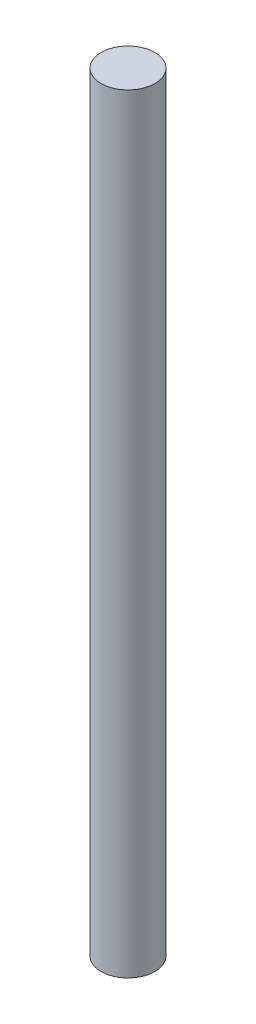
SolidWorks part; units mm, degrees
ref_plane "前视基准面" through (0, 0, 0) normal (0, 0, 1) x (1, 0, 0)
ref_plane "上视基准面" through (0, 0, 0) normal (0, 1, 0) x (1, 0, 0)
ref_plane "右视基准面" through (0, 0, 0) normal (1, 0, 0) x (0, 0, -1)
other "Configuration Table"
sketch "草图1" plane through (0, 0, 0) normal (0, 1, 0) x (1, 0, 0)
  circle A0 centre (0, 0) radius 1.4
  point P0 (-90.6464, 22.0667)
  dimension "D1" = 2.8
extrude "凸台-拉伸1" add sketch "草图1" along normal blind 40
